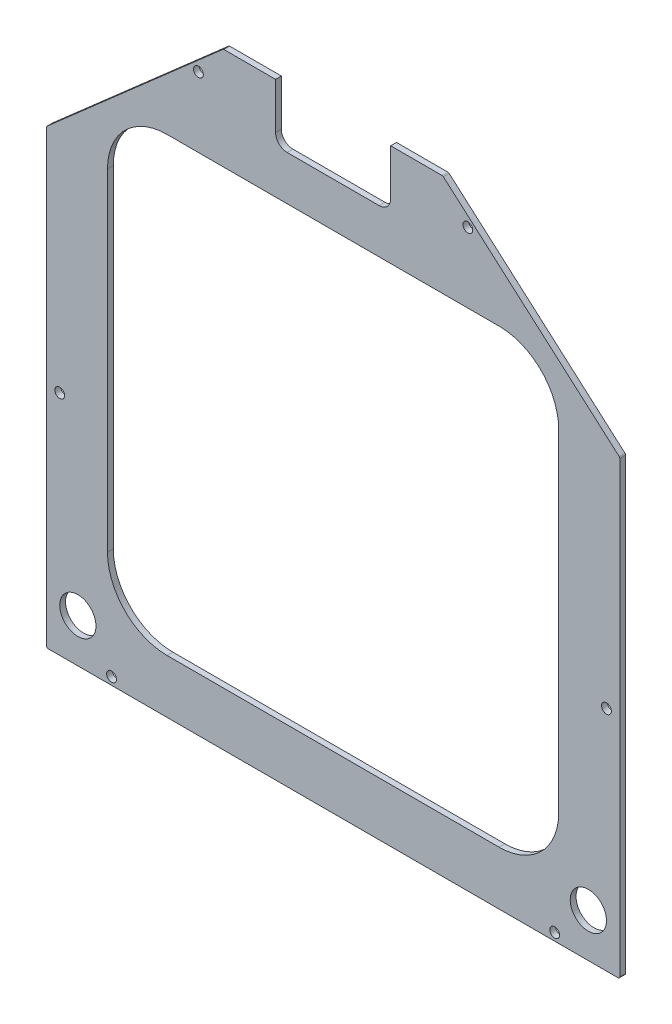
SolidWorks part; units mm, degrees
ref_plane "Front Plane" through (0, 0, 0) normal (0, 0, 1) x (1, 0, 0)
ref_plane "Top Plane" through (0, 0, 0) normal (0, 1, 0) x (1, 0, 0)
ref_plane "Right Plane" through (0, 0, 0) normal (1, 0, 0) x (0, 0, -1)
sketch "Sketch2" plane through (0, 0, 1.5875) normal (0, 0, 1) x (1, 0, 0)
  line L13 (102.87, -114.4519) -> (102.87, -22.8742)
  line L14 (86.4288, -6.433) -> (-5.1489, -6.433)
  line L15 (-21.59, -22.8742) -> (-21.59, -114.4519)
  line L16 (-5.1489, -130.893) -> (86.4288, -130.893)
  line L70 (70.7114, 21.6975) -> (10.5686, 21.6975)
  line L78 (119.5564, -21.0176) -> (71.0466, 21.5712)
  line L79 (119.7292, -145.1805) -> (119.7292, -21.3993)
  line L80 (-37.9413, -145.6885) -> (119.2212, -145.6885)
  line L81 (-38.4493, -21.3993) -> (-38.4493, -145.1805)
  line L82 (10.2334, 21.5712) -> (-38.2764, -21.0176)
  arc A12 (102.87, -22.8742) -> (86.4288, -6.433) centre (86.4288, -22.8742) ccw
  arc A13 (-5.1489, -6.433) -> (-21.59, -22.8742) centre (-5.1489, -22.8742) ccw
  arc A14 (-21.59, -114.4519) -> (-5.1489, -130.893) centre (-5.1489, -114.4519) ccw
  arc A15 (86.4288, -130.893) -> (102.87, -114.4519) centre (86.4288, -114.4519) ccw
  arc A25 (71.0466, 21.5712) -> (70.7114, 21.6975) centre (70.7114, 21.1895) ccw
  arc A62 (119.7292, -21.3993) -> (119.5564, -21.0176) centre (119.2212, -21.3993) ccw
  arc A64 (119.2212, -145.6885) -> (119.7292, -145.1805) centre (119.2212, -145.1805) ccw
  arc A66 (-38.4493, -145.1805) -> (-37.9413, -145.6885) centre (-37.9413, -145.1805) ccw
  arc A68 (-38.2764, -21.0176) -> (-38.4493, -21.3993) centre (-37.9413, -21.3993) ccw
  arc A70 (10.5686, 21.6975) -> (10.2334, 21.5712) centre (10.5686, 21.1895) ccw
extrude "Boss-Extrude1" add sketch "Sketch2" along normal blind 1.6002
sketch "Sketch3" plane through (0, 0, 3.1877) normal (0, 0, 1) x (1, 0, 0)
  circle A2 centre (78.03, -139.5761) radius 0.5
  circle A4 centre (81.28, -140.0261) radius 0.35
  circle A6 centre (81.28, -134.6261) radius 0.35
  circle A8 centre (84.53, -135.0761) radius 0.5
  circle A10 centre (84.53, -139.5761) radius 0.5
  circle A12 centre (-3.25, -139.5761) radius 0.5
  circle A14 centre (-3.25, -135.0761) radius 0.5
  circle A16 centre (0, -134.6261) radius 0.35
  circle A18 centre (57.71, -135.0761) radius 0.5
  circle A20 centre (57.71, -139.5761) radius 0.5
  circle A22 centre (60.96, -134.6261) radius 0.35
  circle A24 centre (60.96, -140.0261) radius 0.35
  circle A26 centre (64.21, -135.0761) radius 0.5
  circle A28 centre (64.21, -139.5761) radius 0.5
  circle A30 centre (78.03, -135.0761) radius 0.5
  circle A32 centre (78.03, -135.0761) radius 0.5
  circle A34 centre (108.7956, -116.6805) radius 0.5
  circle A36 centre (111.0456, -128.0616) radius 1
  circle A38 centre (111.0456, -139.2616) radius 1
  circle A40 centre (103.5456, -136.1616) radius 0.5
  circle A42 centre (103.5456, -133.6616) radius 0.5
  circle A44 centre (103.5456, -131.1616) radius 0.5
  circle A46 centre (43.89, -139.5761) radius 0.5
  circle A48 centre (43.89, -135.0761) radius 0.5
  circle A50 centre (108.3456, -93.1105) radius 0.35
  circle A52 centre (108.7956, -96.3605) radius 0.5
  circle A54 centre (113.2956, -96.3605) radius 0.5
  circle A56 centre (113.2956, -110.1805) radius 0.5
  circle A58 centre (108.7956, -110.1805) radius 0.5
  circle A60 centre (108.3456, -113.4305) radius 0.35
  circle A62 centre (113.7456, -113.4305) radius 0.35
  circle A64 centre (113.2956, -116.6805) radius 0.5
  circle A66 centre (113.2956, -69.5405) radius 0.5
  circle A68 centre (113.7456, -72.7905) radius 0.35
  circle A70 centre (108.3456, -72.7905) radius 0.35
  circle A72 centre (108.7956, -76.0405) radius 0.5
  circle A74 centre (113.2956, -76.0405) radius 0.5
  circle A76 centre (108.7956, -89.8605) radius 0.5
  circle A78 centre (113.2956, -89.8605) radius 0.5
  circle A80 centre (113.7456, -93.1105) radius 0.35
  circle A82 centre (113.2956, -35.4005) radius 0.5
  circle A84 centre (108.7956, -49.2205) radius 0.5
  circle A86 centre (113.2956, -49.2205) radius 0.5
  circle A88 centre (113.7456, -52.4705) radius 0.35
  circle A90 centre (108.3456, -52.4705) radius 0.35
  circle A92 centre (108.7956, -55.7205) radius 0.5
  circle A94 centre (113.2956, -55.7205) radius 0.5
  circle A96 centre (108.7956, -69.5405) radius 0.5
  circle A98 centre (17.07, -2.25) radius 0.5
  circle A100 centre (17.07, 2.25) radius 0.5
  circle A102 centre (20.32, 2.7) radius 0.35
  circle A104 centre (23.57, 2.25) radius 0.5
  circle A106 centre (43.89, -2.25) radius 0.5
  circle A108 centre (40.64, -2.7) radius 0.35
  circle A110 centre (37.39, -2.25) radius 0.5
  circle A112 centre (37.39, 2.25) radius 0.5
  circle A114 centre (40.64, 2.7) radius 0.35
  circle A116 centre (43.89, 2.25) radius 0.5
  circle A118 centre (64.21, -2.25) radius 0.5
  circle A120 centre (60.96, -2.7) radius 0.35
  circle A122 centre (57.71, -2.25) radius 0.5
  circle A124 centre (57.71, 2.25) radius 0.5
  circle A126 centre (60.96, 2.7) radius 0.35
  circle A128 centre (64.21, 2.25) radius 0.5
  circle A130 centre (108.7956, -28.9005) radius 0.5
  circle A132 centre (113.2956, -28.9005) radius 0.5
  circle A134 centre (113.7456, -32.1505) radius 0.35
  circle A136 centre (108.3456, -32.1505) radius 0.35
  circle A138 centre (108.7956, -35.4005) radius 0.5
  circle A140 centre (46.3053, 14.9881) radius 0.5
  circle A142 centre (44.9307, 18.3067) radius 0.5
  circle A144 centre (40.2374, 20.2508) radius 0.5
  circle A146 centre (36.9187, 18.8761) radius 0.5
  circle A148 centre (35.9467, 16.5295) radius 0.5
  circle A150 centre (34.9747, 14.1828) radius 0.5
  circle A152 centre (36.3493, 10.8642) radius 0.5
  circle A154 centre (41.0426, 8.9201) radius 0.5
  circle A156 centre (3.25, -2.25) radius 0.5
  circle A158 centre (0, -2.7) radius 0.35
  circle A160 centre (-3.25, -2.25) radius 0.5
  circle A162 centre (-3.25, 2.25) radius 0.5
  circle A164 centre (0, 2.7) radius 0.35
  circle A166 centre (3.25, 2.25) radius 0.5
  circle A168 centre (23.57, -2.25) radius 0.5
  circle A170 centre (20.32, -2.7) radius 0.35
  circle A172 centre (84.53, -2.25) radius 0.5
  circle A174 centre (84.53, 2.25) radius 0.5
  circle A176 centre (81.28, 2.7) radius 0.35
  circle A178 centre (81.28, -2.7) radius 0.35
  circle A180 centre (78.03, -2.25) radius 0.5
  circle A182 centre (78.03, 2.25) radius 0.5
  circle A184 centre (44.3613, 10.2948) radius 0.5
  circle A186 centre (45.3333, 12.6414) radius 0.5
  circle A188 centre (-27.5156, -28.9005) radius 0.5
  circle A190 centre (-27.5156, -76.0405) radius 0.5
  circle A192 centre (-27.0656, -72.7905) radius 0.35
  circle A194 centre (-32.4656, -72.7905) radius 0.35
  circle A196 centre (-32.0156, -69.5405) radius 0.5
  circle A198 centre (-27.5156, -69.5405) radius 0.5
  circle A200 centre (-32.0156, -55.7205) radius 0.5
  circle A202 centre (-27.5156, -55.7205) radius 0.5
  circle A204 centre (-27.0656, -52.4705) radius 0.35
  circle A206 centre (-32.4656, -52.4705) radius 0.35
  circle A208 centre (-32.0156, -49.2205) radius 0.5
  circle A210 centre (-27.5156, -49.2205) radius 0.5
  circle A212 centre (-32.0156, -35.4005) radius 0.5
  circle A214 centre (-27.5156, -35.4005) radius 0.5
  circle A216 centre (-27.0656, -32.1505) radius 0.35
  circle A218 centre (-32.4656, -32.1505) radius 0.35
  circle A220 centre (-32.0156, -28.9005) radius 0.5
  circle A222 centre (-22.2656, -136.1616) radius 0.5
  circle A224 centre (-29.7656, -139.2616) radius 1
  circle A226 centre (-29.7656, -128.0616) radius 1
  circle A228 centre (-27.5156, -116.6805) radius 0.5
  circle A230 centre (-32.0156, -116.6805) radius 0.5
  circle A232 centre (-32.4656, -113.4305) radius 0.35
  circle A234 centre (-27.0656, -113.4305) radius 0.35
  circle A236 centre (-27.5156, -110.1805) radius 0.5
  circle A238 centre (-32.0156, -110.1805) radius 0.5
  circle A240 centre (-32.0156, -96.3605) radius 0.5
  circle A242 centre (-27.5156, -96.3605) radius 0.5
  circle A244 centre (-27.0656, -93.1105) radius 0.35
  circle A246 centre (-32.4656, -93.1105) radius 0.35
  circle A248 centre (-32.0156, -89.8605) radius 0.5
  circle A250 centre (-27.5156, -89.8605) radius 0.5
  circle A252 centre (-32.0156, -76.0405) radius 0.5
  circle A254 centre (0, -140.0261) radius 0.35
  circle A256 centre (3.25, -139.5761) radius 0.5
  circle A258 centre (3.25, -135.0761) radius 0.5
  circle A260 centre (3.25, -135.0761) radius 0.5
  circle A262 centre (17.07, -139.5761) radius 0.5
  circle A264 centre (17.07, -135.0761) radius 0.5
  circle A266 centre (20.32, -140.0261) radius 0.35
  circle A268 centre (20.32, -134.6261) radius 0.35
  circle A270 centre (23.57, -139.5761) radius 0.5
  circle A272 centre (23.57, -135.0761) radius 0.5
  circle A274 centre (37.39, -135.0761) radius 0.5
  circle A276 centre (37.39, -139.5761) radius 0.5
  circle A278 centre (40.64, -140.0261) radius 0.35
  circle A280 centre (40.64, -134.6261) radius 0.35
  circle A282 centre (-22.2656, -131.1616) radius 0.5
  circle A284 centre (-22.2656, -133.6616) radius 0.5
extrude "Cut-Extrude1" [suppressed] cut sketch "Sketch3" against normal through all
sketch "CoordRef" [suppressed] plane through (0, 0, 1.5875) normal (0, 0, -1) x (-1, 0, 0)
  line L0 (-40.64, 21.1895) -> (-40.64, -145.1805) construction
  line L1 (-70.7114, 21.1895) -> (-10.5686, 21.1895) construction
  line L2 (37.9413, -145.1805) -> (-119.2212, -145.1805) construction
  line L3 (-40.64, -61.9955) -> (37.9413, -61.9955) construction
  line L4 (37.9413, -21.3993) -> (37.9413, -145.1805) construction
hole_wizard "#2 Clearance Hole1" positions "Sketch5" profile "Sketch4" hole size "#2" standard "ANSI Inch" end condition through all
sketch "Sketch5" plane through (0, 0, 3.1877) normal (0, 0, 1) x (1, 0, 0)
  point P0 (3.4817, 12.8551)
  point P3 (77.7983, 12.8551)
  point P6 (-34.7631, -82.9505)
  point P9 (116.0431, -82.9505)
  point P12 (101.7587, -143.593)
  point P15 (-20.4788, -143.593)
sketch "Sketch4" plane through (3.4817, 12.8551, 3.1877) normal (1, 0, 0) x (0, -1, 0)
  line L0 (0, 0) -> (0, 1.6002)
  line L1 (0, 1.6002) -> (1.3525, 1.6002)
  line L2 (1.3525, 1.6002) -> (1.3525, 0)
  line L5 (1.3525, 0) -> (0, 0)
  line L11 (0, -6.35) -> (0, 107.95) construction
  dimension "Thru Hole Dia." = 2.7051
  dimension "Thru Hole Depth" = 1.6002
sketch "Sketch7" plane through (0, 0, 3.1877) normal (0, 0, 1) x (1, 0, 0)
  line L1 (71.7563, 6.1418) -> (9.5499, 6.1418)
  line L2 (71.7563, 6.1418) -> (71.7563, 20.1032)
  line L3 (71.7563, 20.1032) -> (9.5499, 20.1032)
  line L4 (9.5499, 6.1418) -> (9.5499, 20.1032)
  line L5 (71.7563, 6.1418) -> (9.5499, 20.1032) construction
  line L6 (71.7563, 20.1032) -> (9.5499, 6.1418) construction
  point P4 (40.6531, 13.1225)
extrude "Cut-Extrude2" [suppressed] cut sketch "Sketch7" against normal blind 0.0254
sketch "Sketch8" plane through (0, 0, 3.1877) normal (0, 0, 1) x (1, 0, 0)
  line L1 (56.515, 21.6975) -> (24.765, 21.6975)
  line L2 (56.515, 21.6975) -> (56.515, 5.8225)
  line L3 (56.515, 5.8225) -> (24.765, 5.8225)
  line L4 (24.765, 21.6975) -> (24.765, 5.8225)
  line L5 (56.515, 21.6975) -> (24.765, 5.8225) construction
  line L6 (56.515, 5.8225) -> (24.765, 21.6975) construction
  line L7 (70.7114, 21.6975) -> (10.5686, 21.6975) construction
  point P4 (40.64, 13.76)
  point P10 (40.64, 21.6975)
  point P12 (40.64, 21.6975)
  dimension "D1" = 31.75
  dimension "D2" = 15.875
extrude "Cut-Extrude3" cut sketch "Sketch8" against normal through all
fillet "Fillet1" radius 3.175 2 edges at (56.515, 5.8225, 2.3876) (24.765, 5.8225, 2.3876)
hole_wizard "Ø10.0 (10) Diameter Hole1" positions "Sketch12" profile "Sketch10" hole size "Ø10.0" standard "ANSI Metric" end condition through all
sketch "Sketch12" plane through (0, 0, 1.5875) normal (0, 0, -1) x (-1, 0, 0)
  point P0 (-111.0456, -133.6616)
  point P2 (29.7656, -133.6616)
sketch "Sketch10" plane through (111.0456, -133.6616, 1.5875) normal (1, 0, 0) x (0, 1, 0)
  line L0 (0, 0) -> (0, 1.6002)
  line L1 (0, 1.6002) -> (5, 1.6002)
  line L2 (5, 1.6002) -> (5, 0)
  line L5 (5, 0) -> (0, 0)
  line L11 (0, -6.35) -> (0, 107.95) construction
  dimension "Thru Hole Dia." = 10
  dimension "Thru Hole Depth" = 1.6002
